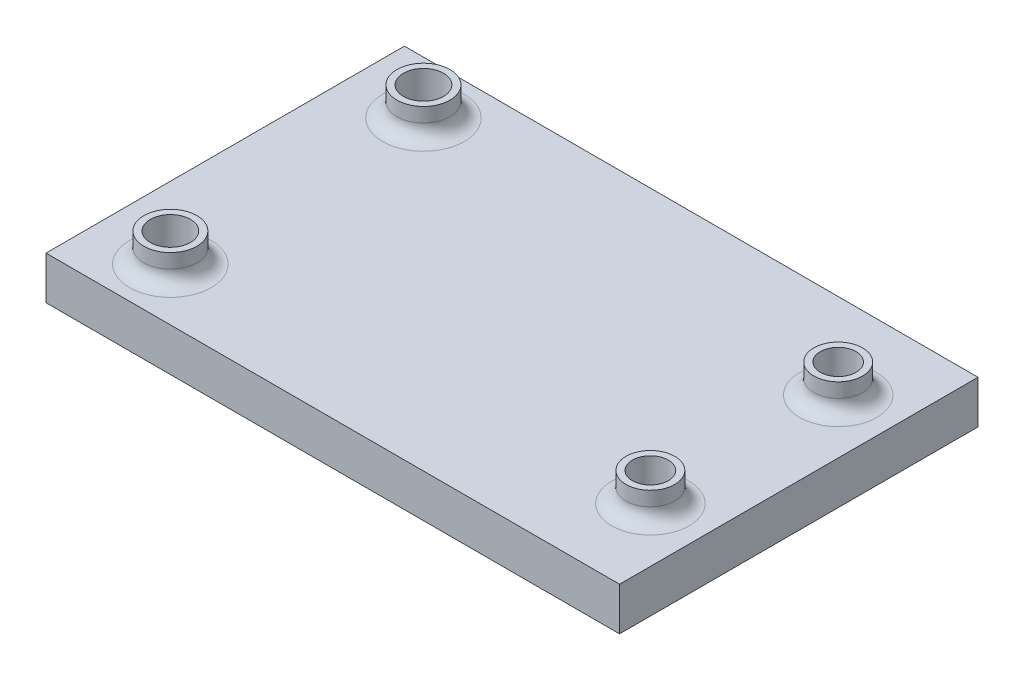
SolidWorks part; units mm, degrees
ref_plane "Front Plane" through (0, 0, 0) normal (0, 0, 1) x (1, 0, 0)
ref_plane "Top Plane" through (0, 0, 0) normal (0, 1, 0) x (1, 0, 0)
ref_plane "Right Plane" through (0, 0, 0) normal (1, 0, 0) x (0, 0, -1)
sketch "Sketch1" plane through (0, 0, 0) normal (0, 1, 0) x (1, 0, 0)
  line L0 (0, 12.5) -> (0, -12.5) construction
  line L1 (-20, 12.5) -> (20, 12.5)
  line L2 (-20, 12.5) -> (-20, -12.5)
  line L3 (-20, -12.5) -> (20, -12.5)
  line L4 (20, 12.5) -> (20, -12.5)
  line L5 (-20, 0) -> (20, 0) construction
  circle A0 centre (-15, 8.825) radius 1.4
  circle A1 centre (-15, -8.825) radius 1.4
  point P13 (0, 0)
  point P14 (0, 0)
  dimension "D3" = 5
  dimension "D4" = 2.8
  dimension "D1" = 40
  dimension "D2" = 25
  dimension "D5" = 17.65
extrude "Boss-Extrude1" add sketch "Sketch1" along normal blind 3
sketch "Sketch2" plane through (0, 3, 0) normal (0, 1, 0) x (1, 0, 0)
  line L0 (0, 0) -> (20, 0) construction
  line L1 (20, -12.5) -> (20, 12.5) construction
  circle A0 centre (16.2, 6.55) radius 1.25
  circle A1 centre (-15, 8.825) radius 1.4 construction
  circle A2 centre (16.2, -6.55) radius 1.25
  dimension "D1" = 31.2
  dimension "D2" = 2.5
  dimension "D3" = 6.55
extrude "Cut-Extrude1" cut sketch "Sketch2" against normal through all
sketch "Sketch4" plane through (0, 3, 0) normal (0, 1, 0) x (1, 0, 0)
  circle A0 centre (-15, 8.825) radius 1.4
  circle A1 centre (-15, 8.825) radius 1.85
  circle A2 centre (16.2, 6.55) radius 1.25
  circle A3 centre (16.2, 6.55) radius 1.7
  circle A4 centre (16.2, -6.55) radius 1.25
  circle A5 centre (16.2, -6.55) radius 1.7
  circle A6 centre (-15, -8.825) radius 1.4
  circle A7 centre (-15, -8.825) radius 1.85
  circle A8 centre (-15, 8.825) radius 1.4 construction
  circle A9 centre (16.2, 6.55) radius 1.25 construction
  dimension "D1" = 3.7
  dimension "D2" = 3.4
extrude "Boss-Extrude2" add sketch "Sketch4" along normal blind 2
fillet "Fillet1" radius 1 4 edges at (16.2, 3, 8.25) (16.2, 3, -4.85) (-15, 3, -6.975) (-15, 3, 10.675)
sketch "Sketch5" plane through (0, 0, 0) normal (0, -1, 0) x (1, 0, 0)
  line L0 (-20, 12.5) -> (20, 12.5) construction
  line L1 (-13.47, 6.175) -> (-11.94, 8.825)
  line L2 (-11.94, 8.825) -> (-13.47, 11.475)
  line L3 (-13.47, 11.475) -> (-16.53, 11.475)
  line L4 (-16.53, 11.475) -> (-18.06, 8.825)
  line L5 (-18.06, 8.825) -> (-16.53, 6.175)
  line L6 (-16.53, 6.175) -> (-13.47, 6.175)
  line L7 (-13.47, -11.475) -> (-11.94, -8.825)
  line L8 (-11.94, -8.825) -> (-13.47, -6.175)
  line L9 (-13.47, -6.175) -> (-16.53, -6.175)
  line L10 (-16.53, -6.175) -> (-18.06, -8.825)
  line L11 (-18.06, -8.825) -> (-16.53, -11.475)
  line L12 (-16.53, -11.475) -> (-13.47, -11.475)
  circle A0 centre (-15, 8.825) radius 2.65 construction
  circle A1 centre (-15, -8.825) radius 2.65 construction
  point P10 (0, 0)
  dimension "D1" = 5.3
extrude "Cut-Extrude2" cut sketch "Sketch5" against normal blind 2
sketch "Sketch6" plane through (0, 0, 0) normal (0, -1, 0) x (1, 0, 0)
  line L0 (20, -12.5) -> (-20, -12.5) construction
  line L1 (17.3836, 4.5) -> (18.5671, 6.55)
  line L2 (18.5671, 6.55) -> (17.3836, 8.6)
  line L3 (17.3836, 8.6) -> (15.0164, 8.6)
  line L4 (15.0164, 8.6) -> (13.8329, 6.55)
  line L5 (13.8329, 6.55) -> (15.0164, 4.5)
  line L6 (15.0164, 4.5) -> (17.3836, 4.5)
  line L7 (17.3836, -8.6) -> (18.5671, -6.55)
  line L8 (18.5671, -6.55) -> (17.3836, -4.5)
  line L9 (17.3836, -4.5) -> (15.0164, -4.5)
  line L10 (15.0164, -4.5) -> (13.8329, -6.55)
  line L11 (13.8329, -6.55) -> (15.0164, -8.6)
  line L12 (15.0164, -8.6) -> (17.3836, -8.6)
  circle A0 centre (16.2, 6.55) radius 2.05 construction
  circle A1 centre (16.2, -6.55) radius 2.05 construction
  dimension "D1" = 4.1
extrude "Cut-Extrude3" cut sketch "Sketch6" against normal blind 1.4
